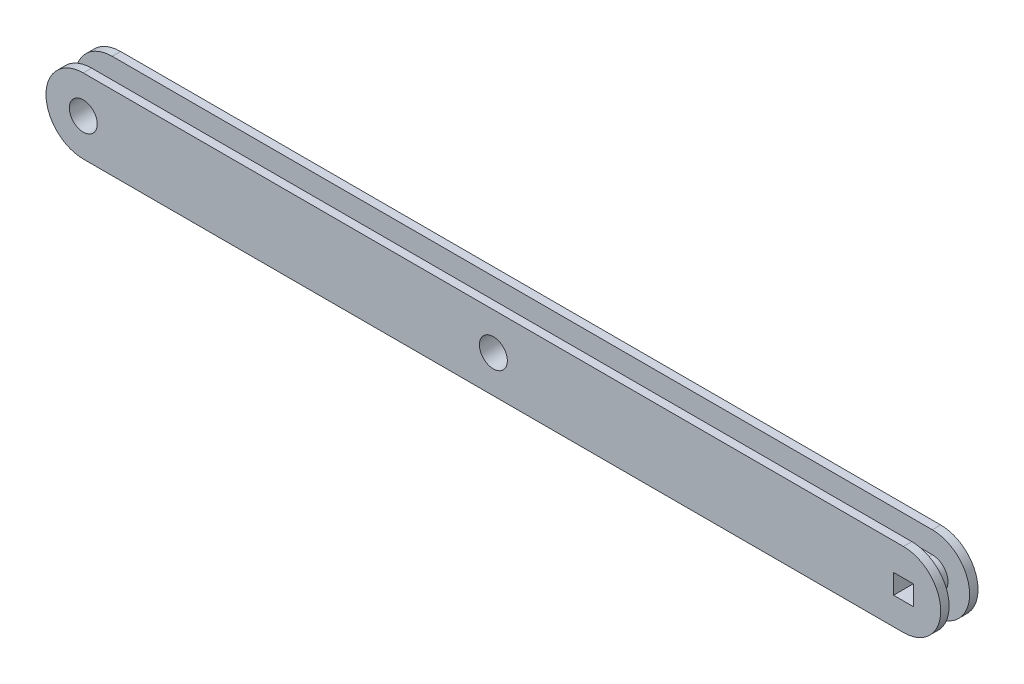
SolidWorks part; units mm, degrees
ref_plane "Plan de face" through (0, 0, 0) normal (0, 0, 1) x (1, 0, 0)
ref_plane "Plan de dessus" through (0, 0, 0) normal (0, 1, 0) x (1, 0, 0)
ref_plane "Plan de droite" through (0, 0, 0) normal (1, 0, 0) x (0, 0, -1)
sketch "Esquisse1" plane through (0, 0, 0) normal (0, 0, 1) x (1, 0, 0)
  line L4 (0, 0) -> (-152.4, 0)
  line L5 (-152.4, 0) -> (-152.4, 12.7)
  line L6 (-152.4, 12.7) -> (0, 12.7)
  line L7 (0, 12.7) -> (0, 0)
  dimension "D1" = 12.7
  dimension "D2" = 152.4
extrude "Boss.-Extru.1" add sketch "Esquisse1" against normal blind 6.35
sketch "Esquisse2" plane through (0, 0, 0) normal (0, 0, 1) x (1, 0, 0)
  line L0 (0, 12.7) -> (-152.4, 12.7) construction
  line L1 (-152.4, 0) -> (0, 0) construction
  line L2 (-152.4, 12.7) -> (-152.4, 0) construction
  line L3 (-6.35, 12.7) -> (0, 12.7)
  line L4 (0, 12.7) -> (0, 0)
  line L5 (0, 0) -> (0, 12.7) construction
  line L6 (0, 0) -> (-6.35, 0)
  line L7 (-146.05, 12.7) -> (-152.4, 12.7)
  line L8 (-152.4, 12.7) -> (-152.4, 0)
  line L9 (-152.4, 0) -> (-146.05, 0)
  line L11 (-8.7313, 3.9687) -> (-3.9688, 3.9687)
  line L12 (-8.7313, 3.9687) -> (-8.7313, 8.7312)
  line L13 (-8.7313, 8.7312) -> (-3.9688, 8.7312)
  line L14 (-3.9688, 3.9687) -> (-3.9688, 8.7312)
  line L15 (-8.7313, 3.9687) -> (-3.9688, 8.7312) construction
  line L16 (-8.7313, 8.7312) -> (-3.9688, 3.9687) construction
  line L17 (-8.0338, 4.6662) -> (-4.6662, 4.6662)
  line L18 (-8.0338, 4.6662) -> (-8.0338, 8.0338)
  line L19 (-8.0338, 8.0338) -> (-4.6662, 8.0338)
  line L20 (-4.6662, 4.6662) -> (-4.6662, 8.0338)
  line L21 (-8.0338, 4.6662) -> (-4.6662, 8.0338) construction
  line L22 (-8.0338, 8.0338) -> (-4.6662, 4.6662) construction
  line L26 (-7.9338, 4.7662) -> (-7.9338, 7.9338)
  line L27 (-7.9338, 7.9338) -> (-4.7662, 7.9338)
  line L28 (-4.7662, 4.7662) -> (-4.7662, 7.9338)
  line L29 (-7.9338, 4.7662) -> (-4.7662, 4.7662)
  circle A0 centre (-146.05, 6.35) radius 2.3813
  circle A1 centre (-6.35, 6.35) radius 2.3813
  circle A2 centre (-76.2, 6.35) radius 2.3813
  arc A3 (-146.05, 12.7) -> (-146.05, 0) centre (-146.05, 6.35) ccw
  arc A4 (-6.35, 12.7) -> (-6.35, 0) centre (-6.35, 6.35) cw
  line M1 (0, 0) -> (0, 12.7)
  line M2 (0, 12.7) -> (-152.4, 12.7)
  line M3 (-152.4, 12.7) -> (-152.4, 0)
  line M4 (-152.4, 0) -> (0, 0)
  dimension "D1" = 4.7625
  dimension "D4" = 4.7625
  dimension "D7" = 4.7625
  dimension "D2" = 6.35
  dimension "D3" = 6.35
  dimension "D5" = 6.35
  dimension "D6" = 6.35
  dimension "D8" = 69.85
  dimension "D9" = 4.7625
  dimension "D10" = 4.7625
  dimension "D11" = 0.1
extrude "Enlèv. mat.-Extru.1" cut sketch "Esquisse2" against normal through all contours A0 | A2 | A4 L4 M2 | A4 M1 M4 | A3 M2 M3 | A3 L8 M4 | L26 L29 L28 L27 | L17 L20 L19 L18 L29 L26 L27 L28 | L26 L27 L28 L29 | L18 L17 L20 L19 region at (-1.4184, 11.2816, 0) region at (-1.4184, 1.4184, 0) region at (-150.9816, 11.2816, 0) region at (-150.9816, 1.4184, 0) region at (-7.9862, 6.35, 0) region at (-6.35, 6.35, 0) region at (-146.05, 6.35, 0) region at (-76.2, 6.35, 0)
ref_plane "Plane1" through (0, 0, -3.175) normal (0, 0, 1) x (1, 0, 0)
ref_plane "Plane2" through (0, 6.35, 0) normal (0, 1, 0) x (1, 0, 0)
sketch "Sketch1" plane through (0, 6.35, 0) normal (0, 1, 0) x (1, 0, 0)
  line L0 (-146.05, 6.35) -> (-146.05, 0) construction
  line L1 (-6.35, 6.35) -> (-146.05, 6.35) construction
  line L2 (-6.35, 0) -> (-146.05, 0) construction
  line L3 (-146.05, 6.35) -> (-146.05, 0) construction
  line L4 (-148.4313, 6.35) -> (-148.4313, 0) construction
  line L5 (-146.05, 6.35) -> (-152.4, 6.35) construction
  line L6 (-152.4, 0) -> (-146.05, 0) construction
  line L7 (-152.4, 4.9225) -> (-150.5585, 4.9225)
  line L8 (-152.4, 6.35) -> (-152.4, 0) construction
  line L11 (-148.717, 4.9225) -> (-148.717, 1.4275)
  line L14 (-150.5585, 1.4275) -> (-152.4, 1.4275)
  line L15 (-152.4, 1.4275) -> (-152.4, 4.9225)
  line L16 (-150.5585, 4.9225) -> (-148.717, 4.9225)
  line L17 (-150.5585, 1.4275) -> (-148.717, 1.4275)
  line L18 (-152.4, 4.9225) -> (-166.5708, 4.9225)
  line L19 (-166.5708, 4.9225) -> (-166.5708, 1.4275)
  line L20 (-166.5708, 1.4275) -> (-152.4, 1.4275)
  point P18 (-148.4313, 3.175)
  point P21 (-148.717, 3.175)
  dimension "D1" = 2.3812
  dimension "D2" = 3.495
  dimension "D4" = 14.1708
  dimension "D5" = 1.8415
revolve "Cut-Revolve1" cut sketch "Sketch1" angle 180 mid plane about L0 region at (-150.5585, 6.35, -3.175) region at (-159.4854, 6.35, -3.175)
ref_plane "Plane3" through (-76.2, 0, 0) normal (1, 0, 0) x (0, 0, -1)
mirror "Mirror1" about plane through (-76.2, 0, 0) normal (1, 0, 0) of "Cut-Revolve1"
sketch "Sketch2" plane through (0, 0, 0) normal (1, 0, 0) x (0, 0, -1)
  line L0 (1.4275, 9.017) -> (1.4275, 12.7) construction
  line L1 (1.4275, 9.017) -> (4.9225, 9.017)
  line L2 (1.4275, 9.017) -> (1.4275, 12.7)
  line L3 (1.4275, 12.7) -> (4.9225, 12.7)
  line L4 (4.9225, 9.017) -> (4.9225, 12.7)
  line L5 (4.9225, 12.7) -> (4.9225, 9.017) construction
  line L6 (4.9225, 12.7) -> (1.4275, 12.7) construction
  line L7 (4.9225, 9.017) -> (1.4275, 9.017) construction
  dimension "D1" = 3.495
extrude "Cut-Extrude1" cut sketch "Sketch2" against normal through all
mirror "Mirror2" about plane through (0, 6.35, 0) normal (0, 1, 0) of "Cut-Extrude1"
ref_plane "Plane4" through (-6.35, 0, 0) normal (1, 0, 0) x (0, 0, -1)
ref_plane "Plane5" through (0, 6.35, 0) normal (0, 1, 0) x (1, 0, 0)
ref_axis "Axis1" through (-6.35, 6.35, -6.6675) along (0, 0, 1)
